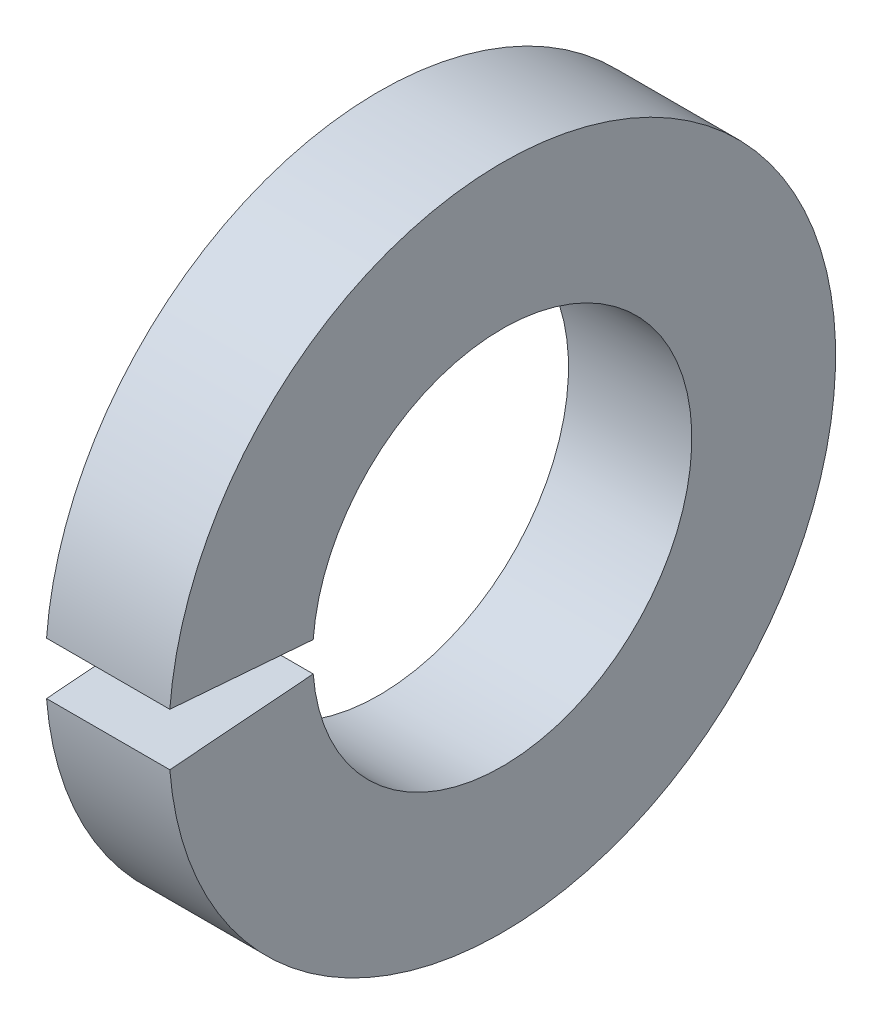
SolidWorks part; units mm, degrees
ref_plane "Plane1" through (0, 0, 0) normal (0, 0, 1) x (1, 0, 0)
ref_plane "Plane2" through (0, 0, 0) normal (0, 1, 0) x (1, 0, 0)
ref_plane "Plane3" through (0, 0, 0) normal (1, 0, 0) x (0, 0, -1)
sketch "Sketch1" plane through (0, 0, 0) normal (0, 0, 1) x (1, 0, 0)
  line L0 (-34.925, 0) -> (9.525, 0) construction
  line L1 (0, 12.8905) -> (0, 22.6695)
  line L2 (0, 22.6695) -> (-8.382, 22.6695)
  line L3 (-8.382, 22.6695) -> (-8.382, 12.8905)
  line L4 (-8.382, 12.8905) -> (0, 12.8905)
  dimension "Thickness" = 8.382
revolve "Base-Revolve" add sketch "Sketch1" angle 360 about L0
sketch "Sketch2" plane through (0, 0, 0) normal (-1, 0, 0) x (0, -1, 0)
  line L0 (0, 0) -> (1.8142, 23.0516)
  line L1 (0, -3.175) -> (0, 12.7) construction
  line L2 (0, 0) -> (-1.8142, 23.0516)
  arc A0 (1.8142, 23.0516) -> (-1.8142, 23.0516) centre (0, 0) ccw
  dimension "D1" = 23.1229
extrude "Gap" cut sketch "Sketch2" along normal through all
equation "\"D1@Sketch2\" = \"Outside_dia@Sketch1\" * 0.51"
